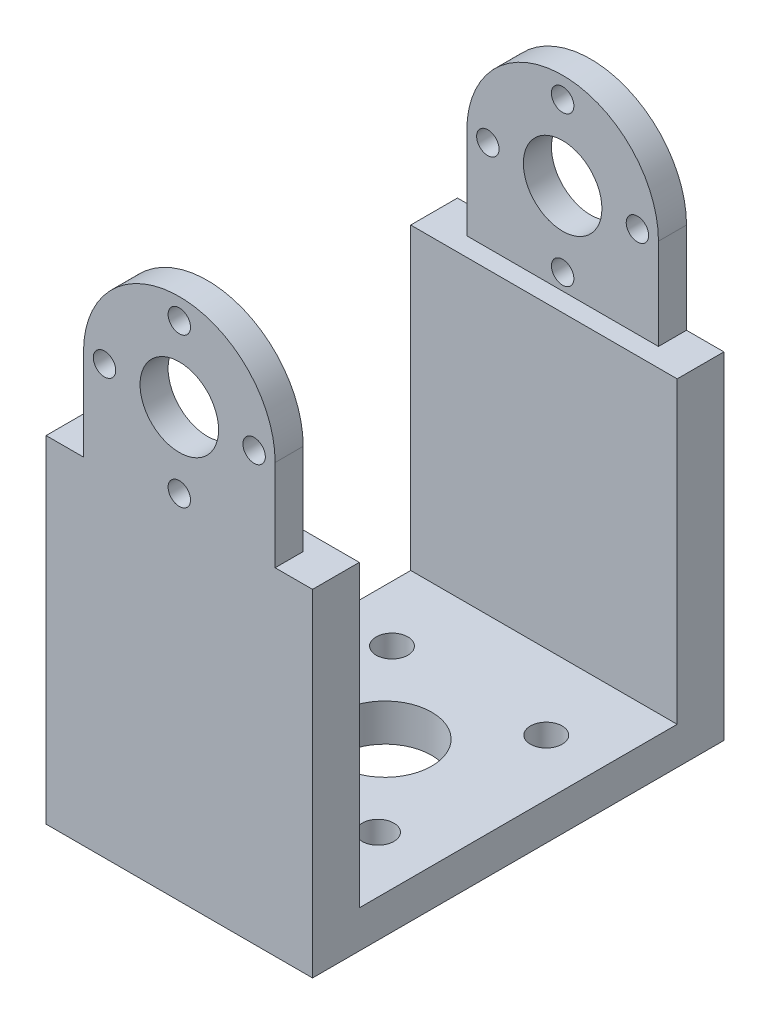
SolidWorks part; units mm, degrees
ref_plane "Front Plane" through (0, 0, 0) normal (0, 0, 1) x (1, 0, 0)
ref_plane "Top Plane" through (0, 0, 0) normal (0, 1, 0) x (1, 0, 0)
ref_plane "Right Plane" through (0, 0, 0) normal (1, 0, 0) x (0, 0, -1)
sketch "Sketch1" plane through (0, 0, 0) normal (0, 0, 1) x (1, 0, 0)
  line L0 (0, 0) -> (0, -100) construction
  line L1 (0, -100) -> (-70, -100) construction
  line L2 (-10.25, -60) -> (-70, -60) construction
  line L4 (-10.25, 0) -> (10.25, 0)
  line L5 (-10.25, 0) -> (-10.25, -60)
  line L7 (10.25, 0) -> (10.25, -60)
  line L8 (-10.25, 0) -> (10.25, 0)
  line L9 (-10.25, 0) -> (-10.25, -100)
  line L10 (-10.25, -100) -> (10.25, -100)
  line L11 (10.25, 0) -> (10.25, -100)
  circle A0 centre (0, 0) radius 10.25
  circle A1 centre (0, 0) radius 8
  circle A2 centre (0, 0) radius 4.2
  circle A3 centre (0, 8) radius 1.2
  circle A4 centre (8, 0) radius 1.2
  circle A5 centre (0, -8) radius 1.2
  circle A6 centre (-8, 0) radius 1.2
  point P16 (0, 0)
  dimension "D1" = 20.5
  dimension "D2" = 16
  dimension "D3" = 8.4
  dimension "D4" = 2.4
  dimension "D6" = 100
  dimension "D7" = 70
  dimension "D8" = 40
  dimension "D5" = 4
extrude "Boss-Extrude1" add sketch "Sketch1" along normal blind 22 and the other way blind 22 contours A0 L5 L7 | A6 L4 A0 A4 A1 A5 | A6 A1 A5 A4 L4 A2 | A6 L4 A2 A4 A1 A3 | A6 A1 A3 A4 L4 A0 region at (8.972, 1.0478, 0) region at (9.725, -0.2292, 0) region at (6.9906, -0.9364, 0) region at (5.5, 0.1769, 0) region at (0, -53.9967, 0)
sketch "Sketch2" plane through (-10.25, 0, 0) normal (-1, 0, 0) x (0, 0, 1)
  line L0 (22, 10.25) -> (-22, 10.25) construction
  line L1 (-19, 10.25) -> (19, 10.25)
  line L2 (-19, 10.25) -> (-19, -9.75)
  line L3 (-19, -9.75) -> (19, -9.75)
  line L4 (19, 10.25) -> (19, -9.75)
  line L5 (22, 0) -> (22, 10.25) construction
  line L6 (-22, 10.25) -> (-22, 0) construction
  dimension "D1" = 3
  dimension "D2" = 3
  dimension "D3" = 20
extrude "Cut-Extrude1" cut sketch "Sketch2" against normal through all
sketch "Sketch3" plane through (0, -9.75, 0) normal (0, 1, 0) x (1, 0, 0)
  line L1 (-10.25, 22) -> (-17.25, 22)
  line L2 (-10.25, 22) -> (-10.25, -22)
  line L3 (-10.25, -22) -> (-17.25, -22)
  line L4 (-17.25, 22) -> (-17.25, -22)
  line L5 (10.25, 22) -> (17.25, 22)
  line L6 (10.25, 22) -> (10.25, -22)
  line L7 (10.25, -22) -> (17.25, -22)
  line L8 (17.25, 22) -> (17.25, -22)
  dimension "D1" = 7
  dimension "D2" = 7
extrude "Boss-Extrude2" add sketch "Sketch3" against normal blind 36
sketch "Sketch5" plane through (-17.25, 0, 0) normal (-1, 0, 0) x (0, 0, 1)
  line L0 (-22, -9.75) -> (22, -9.75) construction
  line L1 (-17, -9.75) -> (17, -9.75)
  line L2 (-17, -9.75) -> (-17, -59.75)
  line L3 (-17, -59.75) -> (17, -59.75)
  line L4 (17, -9.75) -> (17, -59.75)
  line L8 (-19, 0) -> (-19, -9.75) construction
  dimension "D1" = 34
  dimension "D2" = 2
  dimension "D3" = 50
extrude "Cut-Extrude3" cut sketch "Sketch5" against normal through all
sketch "Sketch6" plane through (0, 0, 22) normal (0, 0, 1) x (1, 0, 0)
  line L1 (10.25, -45.75) -> (-10.25, -45.75)
  line L2 (10.25, -45.75) -> (10.25, -100)
  line L3 (10.25, -100) -> (-10.25, -100)
  line L4 (-10.25, -45.75) -> (-10.25, -100)
extrude "Cut-Extrude4" cut sketch "Sketch6" against normal through all
sketch "Sketch20" plane through (0, -45.75, 0) normal (0, -1, 0) x (1, 0, 0)
  line L1 (-17.25, 22) -> (17.25, 22)
  line L2 (-17.25, 22) -> (-17.25, -22)
  line L3 (-17.25, -22) -> (17.25, -22)
  line L4 (17.25, 22) -> (17.25, -22)
  line L5 (-17.25, 17) -> (17.25, 17) construction
  line L6 (17.25, -17) -> (-17.25, -17) construction
  line L8 (-14.25, 17) -> (14.25, 17)
  line L9 (-14.25, 17) -> (-14.25, -17)
  line L10 (-14.25, -17) -> (14.25, -17)
  line L11 (14.25, 17) -> (14.25, -17)
  circle A0 centre (0, 0) radius 5
  circle A2 centre (-8.25, 9) radius 1.7
  circle A3 centre (8.25, 9) radius 1.7
  circle A4 centre (8.25, -9) radius 1.7
  circle A5 centre (-8.25, -9) radius 1.7
  line M7 (-17.25, 17) -> (17.25, 17)
  dimension "D1" = 3
  dimension "D2" = 3
  dimension "D3" = 6
  dimension "D4" = 8
  dimension "D5" = 2
  dimension "D6" = 2
extrude "Boss-Extrude5" add sketch "Sketch20" against normal blind 4 contours L11 L9 L10 A5 A4 A3 A2 A0 M7 region at (0, -45.75, 16.5564)
sketch "Sketch21" plane through (0, 0, -22) normal (0, 0, -1) x (-1, 0, 0)
  line L0 (-17.25, -45.75) -> (17.25, -45.75) construction
  line L1 (-17.25, -9.75) -> (-14.25, -9.75)
  line L2 (-17.25, -9.75) -> (-17.25, -45.75)
  line L3 (-17.25, -45.75) -> (-14.25, -45.75)
  line L4 (-14.25, -9.75) -> (-14.25, -45.75)
  line L6 (17.25, -9.75) -> (14.25, -9.75)
  line L7 (17.25, -9.75) -> (17.25, -45.75)
  line L8 (17.25, -45.75) -> (14.25, -45.75)
  line L9 (14.25, -9.75) -> (14.25, -45.75)
  dimension "D1" = 3
  dimension "D2" = 3
extrude "Cut-Extrude12" cut sketch "Sketch21" against normal through all
